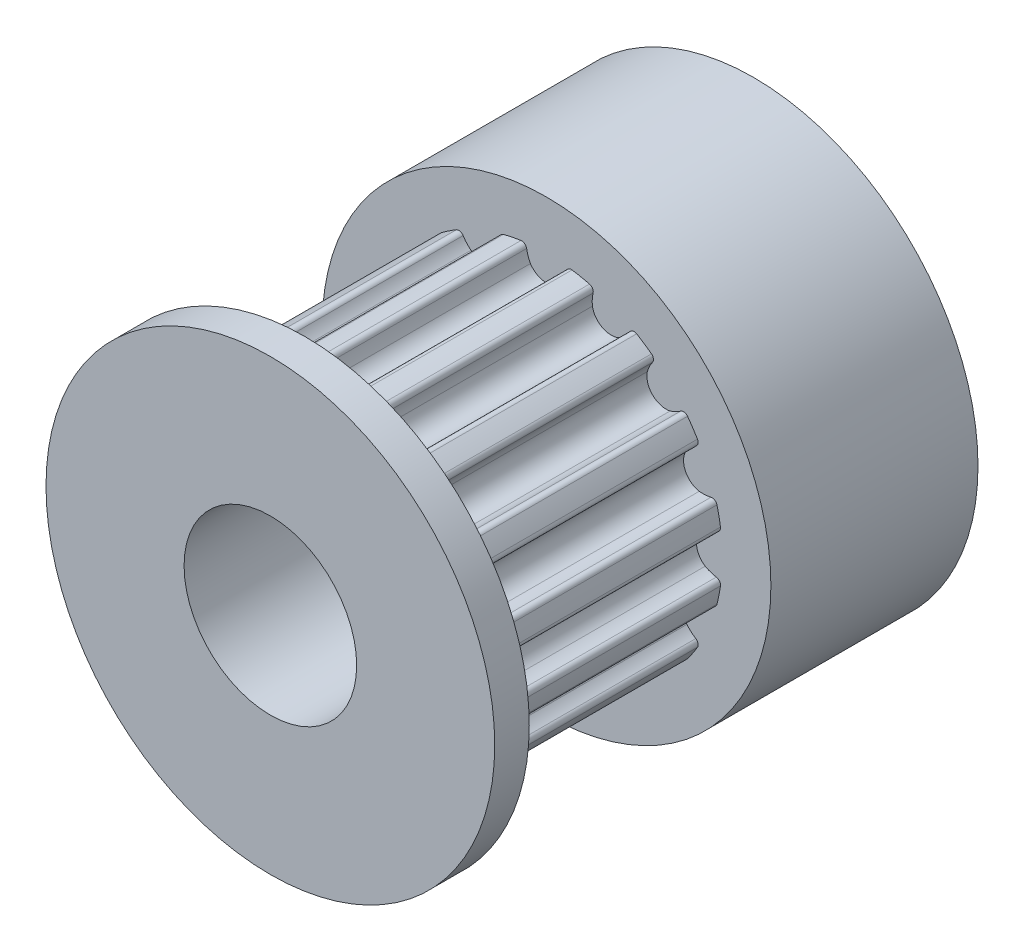
SolidWorks part; units mm, degrees
material "[PLA] Orange"
ref_plane "Front Plane" through (0, 0, 0) normal (0, 0, 1) x (1, 0, 0)
ref_plane "Top Plane" through (0, 0, 0) normal (0, 1, 0) x (1, 0, 0)
ref_plane "Right Plane" through (0, 0, 0) normal (1, 0, 0) x (0, 0, -1)
sketch "Sketch1" plane through (0, 0, 0) normal (0, 0, 1) x (1, 0, 0)
  circle A0 centre (0, 0) radius 6.5
  circle A1 centre (0, 0) radius 2.5
  dimension "D1" = 13
  dimension "D2" = 5
extrude "Boss-Extrude1" add sketch "Sketch1" along normal blind 14
ref_plane "Plane1" through (0, 0, 13) normal (0, 0, 1) x (1, 0, 0)
ref_plane "Plane2" through (0, 0, 6) normal (0, 0, -1) x (-1, 0, 0)
sketch "Sketch2" plane through (0, 0, 6) normal (0, 0, -1) x (-1, 0, 0)
  line L0 (1.949, 4.7053) -> (1.662, 4.0124) construction
  line L1 (3.6013, 3.6013) -> (3.0709, 3.0709) construction
  line L2 (4.7053, 1.949) -> (4.0124, 1.662) construction
  line L3 (0, 5.093) -> (0, 4.343) construction
  line L4 (5.093, 0) -> (4.343, 0) construction
  line L5 (4.7053, -1.949) -> (4.0124, -1.662) construction
  line L6 (3.6013, -3.6013) -> (3.0709, -3.0709) construction
  line L7 (1.949, -4.7053) -> (1.662, -4.0124) construction
  line L8 (0, -5.093) -> (0, -4.343) construction
  line L9 (-1.949, -4.7053) -> (-1.662, -4.0124) construction
  line L10 (-3.6013, -3.6013) -> (-3.0709, -3.0709) construction
  line L11 (-4.7053, -1.949) -> (-4.0124, -1.662) construction
  line L12 (-5.093, 0) -> (-4.343, 0) construction
  line L13 (-4.7053, 1.949) -> (-4.0124, 1.662) construction
  line L14 (-3.6013, 3.6013) -> (-3.0709, 3.0709) construction
  line L15 (-1.949, 4.7053) -> (-1.662, 4.0124) construction
  circle A0 centre (0, 0) radius 4.343 construction
  circle A2 centre (0, 0) radius 5.093 construction
  arc A3 (0.4659, 4.5964) -> (-0.4659, 4.5964) centre (0, 4.898) cw
  arc A4 (-0.4659, 4.5964) -> (-0.5762, 4.9194) centre (0.4114, 5.0763) cw
  arc A5 (-0.5762, 4.9194) -> (-0.739, 5.0391) centre (-0.7182, 4.8969) ccw
  arc A6 (-0.739, 5.0391) -> (-0.9936, 4.9951) centre (0, 0) ccw
  arc A8 (0.739, 5.0391) -> (0.9936, 4.9951) centre (0, 0) cw
  arc A9 (0.5762, 4.9194) -> (0.739, 5.0391) centre (0.7182, 4.8969) cw
  arc A10 (0.4659, 4.5964) -> (0.5762, 4.9194) centre (-0.4114, 5.0763) ccw
  arc A11 (2.1894, 4.0682) -> (1.3285, 4.4248) centre (1.8744, 4.5251) cw
  arc A12 (1.3285, 4.4248) -> (1.3502, 4.7655) centre (2.3227, 4.5325) cw
  arc A13 (1.3502, 4.7655) -> (1.2456, 4.9383) centre (1.2105, 4.7989) ccw
  arc A14 (1.2456, 4.9383) -> (0.9936, 4.9951) centre (0, 0) ccw
  arc A15 (2.6111, 4.3727) -> (2.8295, 4.2346) centre (0, 0) cw
  arc A16 (2.4149, 4.3244) -> (2.6111, 4.3727) centre (2.5374, 4.2493) cw
  arc A17 (2.1894, 4.0682) -> (2.4149, 4.3244) centre (1.5625, 4.8473) ccw
  arc A18 (3.5796, 2.9207) -> (2.9207, 3.5796) centre (3.4634, 3.4634) cw
  arc A19 (2.9207, 3.5796) -> (3.0711, 3.886) centre (3.8804, 3.2986) cw
  arc A20 (3.0711, 3.886) -> (3.0406, 4.0857) centre (2.9548, 3.9704) ccw
  arc A21 (3.0406, 4.0857) -> (2.8295, 4.2346) centre (0, 0) ccw
  arc A22 (4.0857, 3.0406) -> (4.2346, 2.8295) centre (0, 0) cw
  arc A23 (3.886, 3.0711) -> (4.0857, 3.0406) centre (3.9704, 2.9548) cw
  arc A24 (3.5796, 2.9207) -> (3.886, 3.0711) centre (3.2986, 3.8804) ccw
  arc A25 (4.4248, 1.3285) -> (4.0682, 2.1894) centre (4.5251, 1.8744) cw
  arc A26 (4.0682, 2.1894) -> (4.3244, 2.4149) centre (4.8473, 1.5625) cw
  arc A27 (4.3244, 2.4149) -> (4.3727, 2.6111) centre (4.2493, 2.5374) ccw
  arc A28 (4.3727, 2.6111) -> (4.2346, 2.8295) centre (0, 0) ccw
  arc A29 (4.9383, 1.2456) -> (4.9951, 0.9936) centre (0, 0) cw
  arc A30 (4.7655, 1.3502) -> (4.9383, 1.2456) centre (4.7989, 1.2105) cw
  arc A31 (4.4248, 1.3285) -> (4.7655, 1.3502) centre (4.5325, 2.3227) ccw
  arc A32 (4.5964, -0.4659) -> (4.5964, 0.4659) centre (4.898, 0) cw
  arc A33 (4.5964, 0.4659) -> (4.9194, 0.5762) centre (5.0763, -0.4114) cw
  arc A34 (4.9194, 0.5762) -> (5.0391, 0.739) centre (4.8969, 0.7182) ccw
  arc A35 (5.0391, 0.739) -> (4.9951, 0.9936) centre (0, 0) ccw
  arc A36 (5.0391, -0.739) -> (4.9951, -0.9936) centre (0, 0) cw
  arc A37 (4.9194, -0.5762) -> (5.0391, -0.739) centre (4.8969, -0.7182) cw
  arc A38 (4.5964, -0.4659) -> (4.9194, -0.5762) centre (5.0763, 0.4114) ccw
  arc A39 (4.0682, -2.1894) -> (4.4248, -1.3285) centre (4.5251, -1.8744) cw
  arc A40 (4.4248, -1.3285) -> (4.7655, -1.3502) centre (4.5325, -2.3227) cw
  arc A41 (4.7655, -1.3502) -> (4.9383, -1.2456) centre (4.7989, -1.2105) ccw
  arc A42 (4.9383, -1.2456) -> (4.9951, -0.9936) centre (0, 0) ccw
  arc A43 (4.3727, -2.6111) -> (4.2346, -2.8295) centre (0, 0) cw
  arc A44 (4.3244, -2.4149) -> (4.3727, -2.6111) centre (4.2493, -2.5374) cw
  arc A45 (4.0682, -2.1894) -> (4.3244, -2.4149) centre (4.8473, -1.5625) ccw
  arc A46 (2.9207, -3.5796) -> (3.5796, -2.9207) centre (3.4634, -3.4634) cw
  arc A47 (3.5796, -2.9207) -> (3.886, -3.0711) centre (3.2986, -3.8804) cw
  arc A48 (3.886, -3.0711) -> (4.0857, -3.0406) centre (3.9704, -2.9548) ccw
  arc A49 (4.0857, -3.0406) -> (4.2346, -2.8295) centre (0, 0) ccw
  arc A50 (3.0406, -4.0857) -> (2.8295, -4.2346) centre (0, 0) cw
  arc A51 (3.0711, -3.886) -> (3.0406, -4.0857) centre (2.9548, -3.9704) cw
  arc A52 (2.9207, -3.5796) -> (3.0711, -3.886) centre (3.8804, -3.2986) ccw
  arc A53 (1.3285, -4.4248) -> (2.1894, -4.0682) centre (1.8744, -4.5251) cw
  arc A54 (2.1894, -4.0682) -> (2.4149, -4.3244) centre (1.5625, -4.8473) cw
  arc A55 (2.4149, -4.3244) -> (2.6111, -4.3727) centre (2.5374, -4.2493) ccw
  arc A56 (2.6111, -4.3727) -> (2.8295, -4.2346) centre (0, 0) ccw
  arc A57 (1.2456, -4.9383) -> (0.9936, -4.9951) centre (0, 0) cw
  arc A58 (1.3502, -4.7655) -> (1.2456, -4.9383) centre (1.2105, -4.7989) cw
  arc A59 (1.3285, -4.4248) -> (1.3502, -4.7655) centre (2.3227, -4.5325) ccw
  arc A60 (-0.4659, -4.5964) -> (0.4659, -4.5964) centre (0, -4.898) cw
  arc A61 (0.4659, -4.5964) -> (0.5762, -4.9194) centre (-0.4114, -5.0763) cw
  arc A62 (0.5762, -4.9194) -> (0.739, -5.0391) centre (0.7182, -4.8969) ccw
  arc A63 (0.739, -5.0391) -> (0.9936, -4.9951) centre (0, 0) ccw
  arc A64 (-0.739, -5.0391) -> (-0.9936, -4.9951) centre (0, 0) cw
  arc A65 (-0.5762, -4.9194) -> (-0.739, -5.0391) centre (-0.7182, -4.8969) cw
  arc A66 (-0.4659, -4.5964) -> (-0.5762, -4.9194) centre (0.4114, -5.0763) ccw
  arc A67 (-2.1894, -4.0682) -> (-1.3285, -4.4248) centre (-1.8744, -4.5251) cw
  arc A68 (-1.3285, -4.4248) -> (-1.3502, -4.7655) centre (-2.3227, -4.5325) cw
  arc A69 (-1.3502, -4.7655) -> (-1.2456, -4.9383) centre (-1.2105, -4.7989) ccw
  arc A70 (-1.2456, -4.9383) -> (-0.9936, -4.9951) centre (0, 0) ccw
  arc A71 (-2.6111, -4.3727) -> (-2.8295, -4.2346) centre (0, 0) cw
  arc A72 (-2.4149, -4.3244) -> (-2.6111, -4.3727) centre (-2.5374, -4.2493) cw
  arc A73 (-2.1894, -4.0682) -> (-2.4149, -4.3244) centre (-1.5625, -4.8473) ccw
  arc A74 (-3.5796, -2.9207) -> (-2.9207, -3.5796) centre (-3.4634, -3.4634) cw
  arc A75 (-2.9207, -3.5796) -> (-3.0711, -3.886) centre (-3.8804, -3.2986) cw
  arc A76 (-3.0711, -3.886) -> (-3.0406, -4.0857) centre (-2.9548, -3.9704) ccw
  arc A77 (-3.0406, -4.0857) -> (-2.8295, -4.2346) centre (0, 0) ccw
  arc A78 (-4.0857, -3.0406) -> (-4.2346, -2.8295) centre (0, 0) cw
  arc A79 (-3.886, -3.0711) -> (-4.0857, -3.0406) centre (-3.9704, -2.9548) cw
  arc A80 (-3.5796, -2.9207) -> (-3.886, -3.0711) centre (-3.2986, -3.8804) ccw
  arc A81 (-4.4248, -1.3285) -> (-4.0682, -2.1894) centre (-4.5251, -1.8744) cw
  arc A82 (-4.0682, -2.1894) -> (-4.3244, -2.4149) centre (-4.8473, -1.5625) cw
  arc A83 (-4.3244, -2.4149) -> (-4.3727, -2.6111) centre (-4.2493, -2.5374) ccw
  arc A84 (-4.3727, -2.6111) -> (-4.2346, -2.8295) centre (0, 0) ccw
  arc A85 (-4.9383, -1.2456) -> (-4.9951, -0.9936) centre (0, 0) cw
  arc A86 (-4.7655, -1.3502) -> (-4.9383, -1.2456) centre (-4.7989, -1.2105) cw
  arc A87 (-4.4248, -1.3285) -> (-4.7655, -1.3502) centre (-4.5325, -2.3227) ccw
  arc A88 (-4.5964, 0.4659) -> (-4.5964, -0.4659) centre (-4.898, 0) cw
  arc A89 (-4.5964, -0.4659) -> (-4.9194, -0.5762) centre (-5.0763, 0.4114) cw
  arc A90 (-4.9194, -0.5762) -> (-5.0391, -0.739) centre (-4.8969, -0.7182) ccw
  arc A91 (-5.0391, -0.739) -> (-4.9951, -0.9936) centre (0, 0) ccw
  arc A92 (-5.0391, 0.739) -> (-4.9951, 0.9936) centre (0, 0) cw
  arc A93 (-4.9194, 0.5762) -> (-5.0391, 0.739) centre (-4.8969, 0.7182) cw
  arc A94 (-4.5964, 0.4659) -> (-4.9194, 0.5762) centre (-5.0763, -0.4114) ccw
  arc A95 (-4.0682, 2.1894) -> (-4.4248, 1.3285) centre (-4.5251, 1.8744) cw
  arc A96 (-4.4248, 1.3285) -> (-4.7655, 1.3502) centre (-4.5325, 2.3227) cw
  arc A97 (-4.7655, 1.3502) -> (-4.9383, 1.2456) centre (-4.7989, 1.2105) ccw
  arc A98 (-4.9383, 1.2456) -> (-4.9951, 0.9936) centre (0, 0) ccw
  arc A99 (-4.3727, 2.6111) -> (-4.2346, 2.8295) centre (0, 0) cw
  arc A100 (-4.3244, 2.4149) -> (-4.3727, 2.6111) centre (-4.2493, 2.5374) cw
  arc A101 (-4.0682, 2.1894) -> (-4.3244, 2.4149) centre (-4.8473, 1.5625) ccw
  arc A102 (-2.9207, 3.5796) -> (-3.5796, 2.9207) centre (-3.4634, 3.4634) cw
  arc A103 (-3.5796, 2.9207) -> (-3.886, 3.0711) centre (-3.2986, 3.8804) cw
  arc A104 (-3.886, 3.0711) -> (-4.0857, 3.0406) centre (-3.9704, 2.9548) ccw
  arc A105 (-4.0857, 3.0406) -> (-4.2346, 2.8295) centre (0, 0) ccw
  arc A106 (-3.0406, 4.0857) -> (-2.8295, 4.2346) centre (0, 0) cw
  arc A107 (-3.0711, 3.886) -> (-3.0406, 4.0857) centre (-2.9548, 3.9704) cw
  arc A108 (-2.9207, 3.5796) -> (-3.0711, 3.886) centre (-3.8804, 3.2986) ccw
  arc A109 (-1.3285, 4.4248) -> (-2.1894, 4.0682) centre (-1.8744, 4.5251) cw
  arc A110 (-2.1894, 4.0682) -> (-2.4149, 4.3244) centre (-1.5625, 4.8473) cw
  arc A111 (-2.4149, 4.3244) -> (-2.6111, 4.3727) centre (-2.5374, 4.2493) ccw
  arc A112 (-2.6111, 4.3727) -> (-2.8295, 4.2346) centre (0, 0) ccw
  arc A113 (-1.2456, 4.9383) -> (-0.9936, 4.9951) centre (0, 0) cw
  arc A114 (-1.3502, 4.7655) -> (-1.2456, 4.9383) centre (-1.2105, 4.7989) cw
  arc A115 (-1.3285, 4.4248) -> (-1.3502, 4.7655) centre (-2.3227, 4.5325) ccw
  circle A116 centre (0, 0) radius 6.5 construction
  circle A117 centre (0, 0) radius 6.5
  point P251 (0, 0)
  dimension "D1" = 2
  dimension "D3" = 0.555
  dimension "D7" = 16
  dimension "D2" = 0.75
extrude "Cut-Extrude1" cut sketch "Sketch2" against normal up to surface (7 mm away) up to plane "Plane1"
